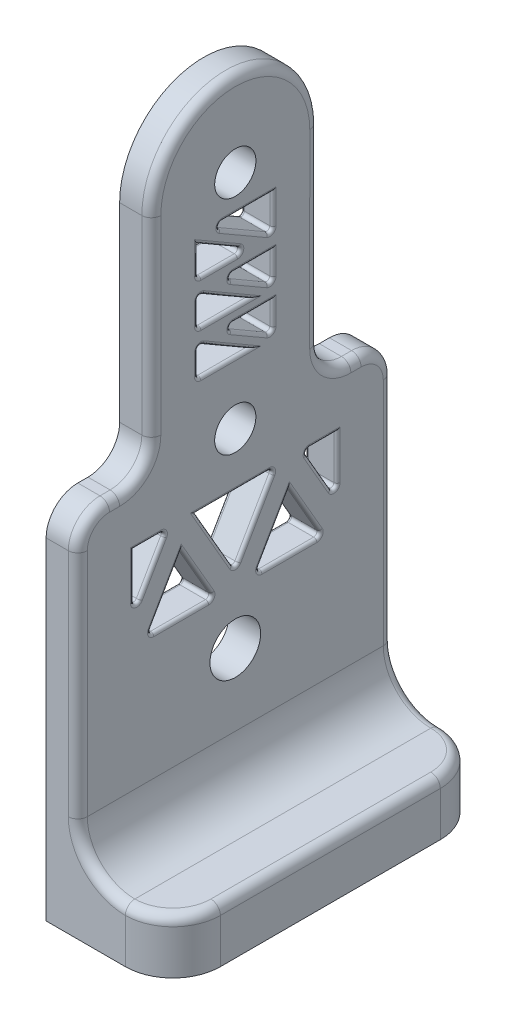
SolidWorks part; units mm, degrees
note: The reader was unsure of these and kept them because the rebuilt part matched: shared geometry of "Sketch2<14>".
ref_plane "Front Plane" through (0, 0, 0) normal (0, 0, 1) x (1, 0, 0)
ref_plane "Top Plane" through (0, 0, 0) normal (0, 1, 0) x (1, 0, 0)
ref_plane "Right Plane" through (0, 0, 0) normal (1, 0, 0) x (0, 0, -1)
sketch "Sketch2" plane through (0, 0, 0) normal (1, 0, 0) x (0, 0, -1)
  line L0 (-49.7, 0) -> (-49.7, -54.7)
  line L1 (-49.7, -54.7) -> (49.7, -54.7)
  line L2 (49.7, -54.7) -> (49.7, 0)
  line L3 (-49.7, -37.7) -> (49.7, -37.7)
  line L4 (-49.7, 0) -> (-49.7, 130)
  line L6 (49.7, 130) -> (49.7, 0)
  line L7 (-4.0065, 60) -> (3.9935, 60) construction
  line L8 (-0.0065, 60) -> (0, 130) construction
  line L9 (0, -54.7) -> (0, -37.7) construction
  line L10 (-49.7, 130) -> (49.7, 130) construction
  arc A137 (49.7, 130) -> (-49.7, 130) centre (0, 130) ccw
  circle A138 centre (-0.0065, 60) radius 6.5
  circle A139 centre (0, 130) radius 6.5
  circle A140 centre (0, 0) radius 8
  dimension "D1" = 130
  dimension "D4" = 17
  dimension "D2" = 54.7
  dimension "D3" = 70
extrude "Boss-Extrude1" add sketch "Sketch2" along normal blind 10 contours L6 A137 L4 L0 L3 L2 A140 A139 A138
extrude "Boss-Extrude2" add sketch "Sketch2<14>" along normal blind 40 contours L3 L0 L1 L2
sketch "Sketch2<14>" plane through (0, 0, 0) normal (1, 0, 0) x (0, 0, -1) same geometry as "Sketch2"
sketch "Sketch10" plane through (0, 0, 0) normal (-1, 0, 0) x (0, 0, 1)
  line L0 (0, 130) -> (0.0065, 60) construction
  line L1 (0.0065, 60) -> (49.7, 60) construction
  line L2 (26.5, 130) -> (26.5, 60)
  line L3 (-49.7, 130) -> (-49.7, -54.7)
  line L4 (-49.7, -54.7) -> (49.7, -54.7)
  line L5 (49.7, -54.7) -> (49.7, 130)
  line L8 (49.7, 60) -> (49.7, 130)
  line L9 (26.5, 60) -> (49.7, 60)
  line L10 (-26.4871, 59.9951) -> (-49.6871, 59.9908)
  line L11 (-26.5, 129.9951) -> (-26.4871, 59.9951)
  line L14 (-49.7, 130) -> (-51.6635, 100)
  line L15 (-51.6635, 100) -> (-51.6635, 59.984)
  line L16 (-51.6635, 59.984) -> (-49.6871, 59.9908)
  circle A0 centre (0.0065, 60) radius 6.5 construction
  arc A1 (49.7, 130) -> (-49.7, 130) centre (0, 130) ccw
  arc A2 (49.7, 130) -> (-49.7, 130) centre (0, 130) ccw
  circle A3 centre (0, 130) radius 6.5 construction
  circle A4 centre (0.0065, 60) radius 6.5
  circle A5 centre (0, 130) radius 6.5
  arc A6 (26.5, 130) -> (-26.5, 129.9951) centre (0, 130) ccw
  dimension "D2" = 20
  dimension "D1" = 0
extrude "Cut-Extrude1" cut sketch "Sketch10" against normal blind 10
fillet "Fillet1" radius 10 2 edges at (5, 60, 26.5) (5, 59.9951, -26.4871)
fillet "Fillet2" radius 10 2 edges at (5, 60, 49.7) (5, 59.9908, -49.7)
fillet "Fillet3" radius 15 3 edges at (40, -46.2, -49.7) (10, -37.7, 0) (40, -46.2, 49.7)
fillet "Fillet4" radius 3 16 edges at (10, 100, 26.5) (10, 62.9289, 29.4289) (10, 60, 38.1) (10, 57.0711, 46.7711) (10, 13.65, 49.7) (14.3934, -33.3066, 49.7) (35.6066, -37.7, 45.3066) (40, -37.7, 0) (35.6066, -37.7, -45.3066) (14.3934, -33.3066, -49.7) (10, 13.6463, -49.7) (10, 57.0631, -46.7717) (10, 59.993, -38.0945) (10, 62.9235, -29.4166) (10, 99.9951, -26.4945) (10, 156.5, -0.0024)
sketch "Sketch11" plane through (10, 0, 0) normal (1, 0, 0) x (0, 0, -1)
  line L0 (-0.0065, 60) -> (0, 43) construction
  line L2 (-32.0845, 43) -> (32.0845, 43)
  line L3 (-32.0845, 43) -> (-32.0845, 17)
  line L4 (-32.0845, 17) -> (32.0845, 17)
  line L5 (32.0845, 43) -> (32.0845, 17)
  line L8 (0, 43) -> (0, 17) construction
  line L11 (-27.4657, 17) -> (-17.0734, 35)
  line L12 (-17.0734, 35) -> (-6.6811, 17)
  line L13 (32.0845, 25) -> (21.6922, 43)
  line L14 (12.4546, 43) -> (-1.4018, 19)
  line L15 (-32.0845, 25) -> (-21.6922, 43)
  line L16 (-12.4546, 43) -> (1.4018, 19)
  line L17 (27.4657, 17) -> (17.0734, 35)
  line L18 (17.0734, 35) -> (5.5264, 15)
  point P4 (0, 30)
extrude "Cut-Extrude2" cut sketch "Sketch11" against normal blind 10 contours L17 L18 L4 | L13 L5 L2 | L2 L16 L14 | L12 L11 L4 | L3 L15 L2
fillet "Fillet5" radius 1 40 edges at (0, 34, 32.0845) (10, 34, 32.0845) (0, 43, 26.8883) (10, 43, 26.8883) (0, 26, 22.2695) (10, 26, 22.2695) (0, 26, 11.8772) (10, 26, 11.8772) (0, 32.214, 6.2273) (10, 32.214, 6.2273) (0, 43, 0) (10, 43, 0) (0, 26, -11.8772) (10, 26, -11.8772) (0, 26, -22.2695) (10, 26, -22.2695) (0, 43, -26.8883) (10, 43, -26.8883) (0, 34, -32.0845) (10, 34, -32.0845) (5, 25, 32.0845) (0, 34, 26.8883) (5, 43, 21.6922) (10, 34, 26.8883) (5, 17, 27.4657) (0, 17, 17.0734) (5, 17, 6.6811) (10, 17, 17.0734) (5, 21.428, 0) (0, 32.214, -6.2273) (5, 43, -12.4546) (10, 32.214, -6.2273) (5, 17, -6.6811) (0, 17, -17.0734) (5, 17, -27.4657) (10, 17, -17.0734) (5, 43, -21.6922) (0, 34, -26.8883) (5, 25, -32.0845) (10, 34, -26.8883)
sketch "Sketch13" plane through (10, 0, 0) normal (1, 0, 0) x (0, 0, -1)
  line L0 (0, 130) -> (0, 118.6831) construction
  line L1 (-11.8762, 118.6831) -> (11.8762, 118.6831)
  line L10 (-11.8762, 118.6831) -> (-11.8762, 71.3169)
  line L11 (-11.8762, 71.3169) -> (11.8762, 71.3169)
  line L12 (11.8762, 118.6831) -> (11.8762, 71.3169)
  line L13 (-11.8762, 118.6831) -> (11.8762, 104.9696)
  line L14 (11.8762, 104.9696) -> (-11.8762, 104.9696)
  line L15 (19.3403, 75.5427) -> (-4.4121, 75.5427) construction
  line L16 (-4.4121, 89.2562) -> (19.3403, 75.5427) construction
  line L21 (-12.8762, 116.9511) -> (4.4121, 106.9696) construction
  line L23 (-11.8762, 104.9696) -> (11.8762, 91.2562)
  line L24 (11.8762, 91.2562) -> (-11.8762, 91.2562)
  line L25 (-11.8762, 91.2562) -> (11.8762, 77.5427)
  line L26 (11.8762, 77.5427) -> (-11.8762, 77.5427)
  line L27 (-11.8762, 77.5427) -> (-0.0004, 70.6861)
  line L28 (-11.8762, 116.3737) -> (4.4121, 106.9696)
  line L29 (4.4121, 106.9696) -> (-11.8762, 106.9696)
  line L30 (-11.8762, 102.6602) -> (4.4121, 93.2562)
  line L31 (4.4121, 93.2562) -> (-11.8762, 93.2562)
  line L32 (-11.8762, 88.9468) -> (4.4121, 79.5427)
  line L33 (4.4121, 79.5427) -> (-11.8762, 79.5427)
  line L34 (-11.8762, 75.2333) -> (-5.0928, 71.3169)
  line L35 (-7.8762, 118.6831) -> (11.8762, 107.279)
  line L36 (11.8762, 102.9696) -> (-4.4121, 102.9696)
  line L37 (-4.4121, 102.9696) -> (11.8762, 93.5656)
  line L38 (11.8762, 89.2562) -> (-4.4121, 89.2562)
  line L39 (-4.4121, 89.2562) -> (11.8762, 79.8521)
  line L40 (11.8762, 75.5427) -> (-4.4121, 75.5427)
  line L41 (-4.4121, 75.5427) -> (2.9072, 71.3169)
  line L42 (4.4121, 106.9696) -> (-19.3403, 106.9696) construction
  line L43 (-19.3403, 106.9696) -> (4.4121, 93.2562) construction
  line L44 (4.4121, 93.2562) -> (-19.3403, 93.2562) construction
  line L45 (-19.3403, 93.2562) -> (4.4121, 79.5427) construction
  line L46 (4.4121, 79.5427) -> (-19.3403, 79.5427) construction
  line L47 (-19.3403, 79.5427) -> (10.8762, 62.0971) construction
  line L48 (-0.0004, 70.6861) -> (0, 71.3169) construction
  line L49 (-11.8762, 77.5427) -> (11.8762, 63.8292) construction
  line L50 (-4.4121, 75.5427) -> (12.8762, 65.5613) construction
  line L51 (19.3403, 89.2562) -> (-4.4121, 89.2562) construction
  line L52 (-4.4121, 102.9696) -> (19.3403, 89.2562) construction
  line L53 (19.3403, 102.9696) -> (-4.4121, 102.9696) construction
  line L54 (-10.8762, 120.4152) -> (19.3403, 102.9696) construction
  point P0 (0, 95)
  dimension "D1" = 30
  dimension "D2" = 30
  dimension "D3" = 30
  dimension "D4" = 30
  dimension "D5" = 2
  dimension "D6" = 2
extrude "Cut-Extrude5" cut sketch "Sketch13" against normal blind 10 contours L33 L32 L10 | L38 L39 L12 | L31 L30 L10 | L36 L37 L12 | L29 L28 L10 | L1 L35 L12
fillet "Fillet6" radius 1 48 edges at (0, 118.6831, -2) (10, 118.6831, -2) (0, 112.9811, -11.8762) (10, 112.9811, -11.8762) (10, 97.9582, 3.7321) (0, 93.2562, 3.7321) (10, 93.2562, 3.7321) (0, 89.2562, -3.7321) (10, 89.2562, -3.7321) (0, 84.5541, -11.8762) (10, 84.5541, -11.8762) (0, 84.2447, 3.7321) (10, 84.2447, 3.7321) (0, 79.5427, 3.7321) (10, 79.5427, 3.7321) (5, 118.6831, 7.8762) (0, 112.9811, -2) (5, 107.279, -11.8762) (10, 112.9811, -2) (5, 102.6602, 11.8762) (0, 97.9582, 11.8762) (5, 93.2562, 11.8762) (10, 97.9582, 11.8762) (5, 89.2562, 4.4121) (0, 84.5541, -3.7321) (5, 79.8521, -11.8762) (10, 84.5541, -3.7321) (5, 88.9468, 11.8762) (0, 84.2447, 11.8762) (5, 79.5427, 11.8762) (10, 84.2447, 11.8762) (5, 106.9696, 11.8762) (0, 97.9582, 3.7321) (0, 102.9696, -3.7321) (10, 102.9696, -3.7321) (0, 98.2676, -11.8762) (10, 98.2676, -11.8762) (0, 111.6717, 11.8762) (10, 111.6717, 11.8762) (0, 111.6717, 3.7321) (10, 111.6717, 3.7321) (5, 102.9696, 4.4121) (0, 98.2676, -3.7321) (5, 93.5656, -11.8762) (10, 98.2676, -3.7321) (0, 106.9696, 3.7321) (5, 106.9696, -4.4121) (10, 106.9696, 3.7321)
